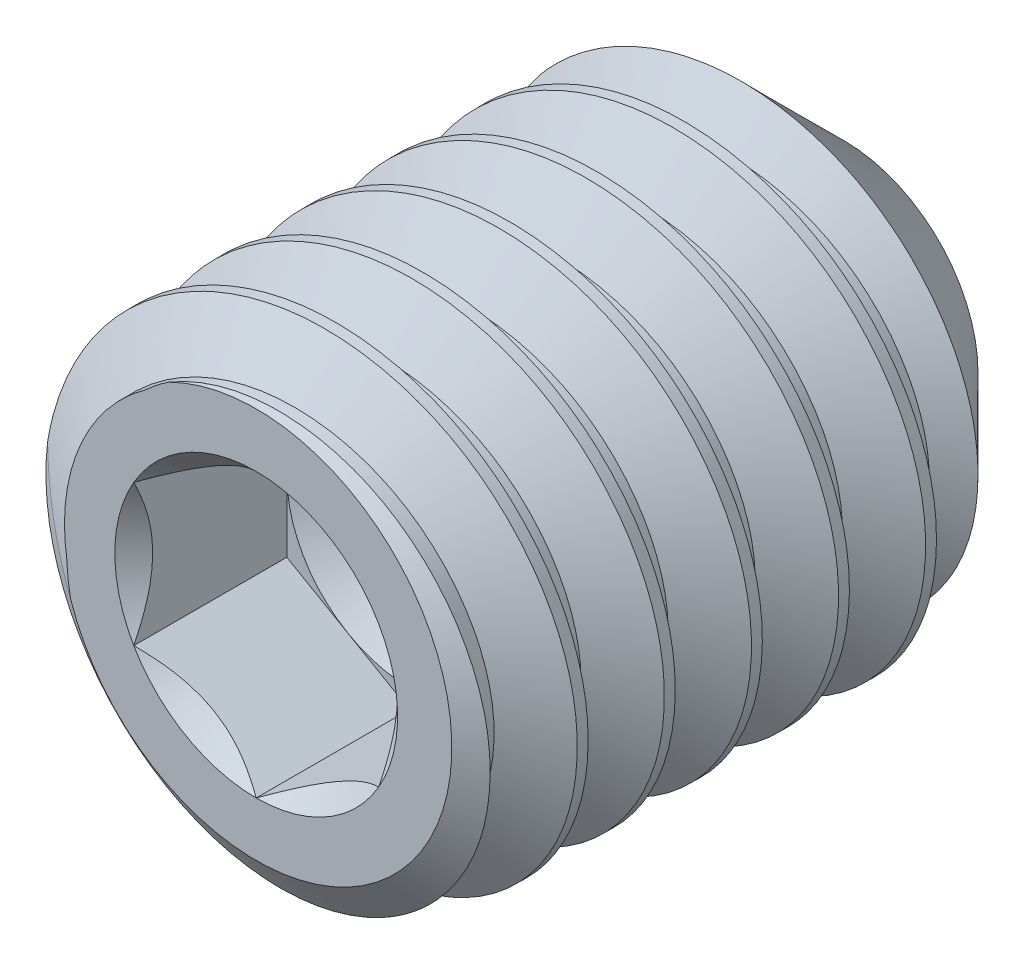
SolidWorks part; units mm, degrees
ref_plane "Front" through (0, 0, 0) normal (0, 0, 1) x (1, 0, 0)
ref_plane "Top" through (0, 0, 0) normal (0, 1, 0) x (1, 0, 0)
ref_plane "Right" through (0, 0, 0) normal (1, 0, 0) x (0, 0, -1)
sketch "Sketch22" plane through (0, 0, 0) normal (1, 0, 0) x (0, 0, -1)
  line L0 (-4.1102, 0) -> (-4.1102, 3.1699)
  line L1 (-4.1102, 3.1699) -> (-3.5553, 3.9624)
  line L2 (-3.5553, 3.9624) -> (3.6237, 3.9624)
  line L3 (3.6237, 3.9624) -> (5.4148, 2.1713)
  line L4 (5.4148, 2.1713) -> (4.1102, 0)
  line L5 (4.1102, 0) -> (-4.1102, 0)
  line L6 (4.1102, 0) -> (5.4148, 0) construction
  line L7 (5.4148, 0) -> (5.4148, 2.1713) construction
  line L8 (5.4148, -2.1713) -> (4.1102, 0) construction
  line L9 (-3.5553, -3.9624) -> (3.6237, -3.9624) construction
  dimension "Dia" = 7.9248
  dimension "Length" = 9.525
  dimension "D3" = 35
  dimension "D5" = 118
  dimension "D6" = 45
  dimension "D7" = 6.3398
revolve "Revolve1" add sketch "Sketch22" angle 360 about L6
ref_plane "Plane1" through (0, 0, -5.4148) normal (0, 0, 1) x (1, 0, 0)
sketch "Sketch27" plane through (0, 0, -5.4148) normal (0, 0, 1) x (1, 0, 0)
  circle A0 centre (0, 0) radius 3.9624 construction
  circle A1 centre (0, 0) radius 3.9624
curve "Helix/Spiral1" pitch 1.4111 height 12.2671 radius 3.9624 centre (0, 0, -5.4148) axis (0, 0, 1) start towards (1, 0, 0)
sketch "Sketch28" plane through (0, 0, 0) normal (1, 0, 0) x (0, 0, -1)
  line L0 (5.4148, 3.9624) -> (6.6495, 3.9624)
  line L1 (6.6495, 3.9624) -> (6.1556, 3.107)
  line L2 (6.1556, 3.107) -> (5.9087, 3.107)
  line L3 (5.9087, 3.107) -> (5.4148, 3.9624)
  line L4 (5.6618, 3.5347) -> (6.4026, 3.5347) construction
  line L6 (-3.5553, 3.9624) -> (3.6237, 3.9624) construction
  line L7 (5.4148, 4.3641) -> (5.4148, -4.3641) construction
  dimension "D3" = 60
  dimension "D2" = 1.2347
sweep "Cut-Sweep2" cut profiles "Sketch28" path "Helix/Spiral1" align with end faces yes
sketch "Sketch23" plane through (0, 0, 4.1102) normal (0, 0, 1) x (1, 0, 0)
  line L1 (0, 2.2914) -> (-1.9844, 1.1457)
  line L2 (-1.9844, 1.1457) -> (-1.9844, -1.1457)
  line L3 (-1.9844, -1.1457) -> (0, -2.2914)
  line L4 (0, -2.2914) -> (1.9844, -1.1457)
  line L5 (1.9844, -1.1457) -> (1.9844, 1.1457)
  line L6 (1.9844, 1.1457) -> (0, 2.2914)
  circle A0 centre (0, 0) radius 1.9844 construction
  dimension "Hex" = 3.9688
extrude "Cut-Extrude10" cut sketch "Sketch23" against normal blind 2.4805
sketch "Sketch24" plane through (0, 0, 4.1102) normal (0, 0, 1) x (1, 0, 0)
  circle A0 centre (0, 0) radius 2.2914
extrude "Cut-Extrude11" cut sketch "Sketch24" against normal through all draft 45
sketch "Sketch26" plane through (0, 0, 1.6297) normal (0, 0, 1) x (1, 0, 0)
  circle A0 centre (0, 0) radius 1.9844 construction
  circle A1 centre (0, 0) radius 1.9844
extrude "Cut-Extrude12" cut sketch "Sketch26" against normal through all draft 60
sketch "Sketch30" plane through (0, 0, 0) normal (1, 0, 0) x (0, 0, -1)
  line L0 (-3.5553, 3.9624) -> (3.6237, 3.9624) construction
  line L1 (-4.1102, 0) -> (-4.1102, 3.1699) construction
  line L2 (5.4148, 0) -> (5.4148, 2.1713) construction
  line L3 (-3.5553, -3.9624) -> (3.6237, -3.9624) construction
  point P0 (-4.1102, 3.9624)
  point P1 (5.4148, 3.9624)
  point P2 (5.4148, -3.9624)
  point P11 (1.887, -3.9624)
  dimension "D1" = 3.5278
sketch "Sketch31" plane through (0, 0, 0) normal (1, 0, 0) x (0, 0, -1)
  line L2 (4.1102, 0) -> (5.4148, -2.1713)
  line L3 (5.4148, 2.1713) -> (4.1102, 0)
equation "\"D7@Sketch22\"=\"Dia@Sketch22\"*.8"
equation "\"D1@Sketch28\" = \"D4@Helix/Spiral1\" * .175"
equation "\"D3@Helix/Spiral1\" = \"Length@Sketch22\" + \"D4@Helix/Spiral1\" + .0524"
equation "\"D1@Sketch30\" = \"D4@Helix/Spiral1\" * 2.5"
equation "\"hex Depth@Cut-Extrude10\" = \"Hex@Sketch23\" * .625"
equation "\"D2@Sketch28\" = \"D4@Helix/Spiral1\" * .875"
